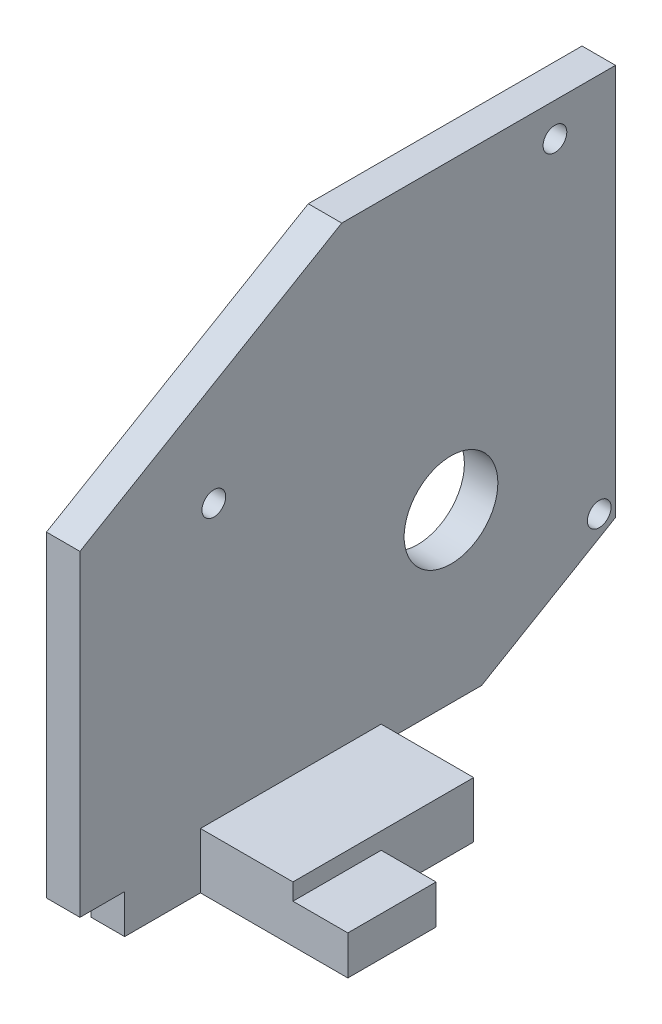
SolidWorks part; units mm, degrees
material "BRASS"
ref_plane "Front Plane" through (0, 0, 0) normal (0, 0, 1) x (1, 0, 0)
ref_plane "Top Plane" through (0, 0, 0) normal (0, 1, 0) x (1, 0, 0)
ref_plane "Right Plane" through (0, 0, 0) normal (1, 0, 0) x (0, 0, -1)
sketch "Sketch2" plane through (0, 0, 0) normal (1, 0, 0) x (0, 0, -1)
  line L6 (0, 0) -> (76.2, 0)
  line L7 (76.2, 0) -> (101.6111, 14.8934)
  line L10 (49.67, 89.2456) -> (0, 60.1339)
  line L12 (49.67, 89.2456) -> (101.6111, 89.1932)
  line L13 (101.6111, 89.1932) -> (101.6111, 14.8934)
  line L15 (0, 60.1339) -> (0, 0)
  line L16 (22.86, 0) -> (22.86, 3.175)
  line L17 (57.15, 0) -> (57.15, 3.175)
  line L18 (44.45, 0) -> (44.45, 3.175) construction
  line L19 (31.75, 0) -> (31.75, 3.175) construction
  line L20 (22.86, 3.175) -> (57.15, 3.175)
  line L21 (57.15, 0) -> (57.15, -7.4092)
  line L22 (57.15, -7.4092) -> (8.4806, -7.4092)
  line L23 (4.9187, -7.4092) -> (19.3272, -7.4092) construction
  line L24 (8.4806, -7.4092) -> (8.4806, 0)
  line L25 (22.86, 0) -> (22.86, -7.4092)
  line L26 (25.4, 55.3212) -> (70.4004, 31.75) construction
  line L27 (70.4004, 31.75) -> (98.5257, 17.018) construction
  circle A0 centre (25.4, 55.3212) radius 2.2479
  circle A1 centre (90.1192, 82.8548) radius 2.2479
  circle A3 centre (25.4, 55.3212) radius 50.8 construction
  circle A4 centre (70.4004, 31.75) radius 31.75 construction
  circle A5 centre (70.4004, 31.75) radius 8.89
  circle A6 centre (98.5257, 17.018) radius 2.2479
  point P22 (0, 0)
  point P23 (101.6111, 14.8934)
  point P30 (70.4004, 31.75)
  point P34 (0, 0)
  dimension "D3" = 4.4958
  dimension "D14" = 101.6
  dimension "D16" = 63.5
  dimension "D17" = 17.78
  dimension "D1" = 76.2
  dimension "D2" = 25.4
  dimension "D4" = 55.3212
  dimension "D5" = 82.8548
  dimension "D6" = 70.3326
  dimension "D7" = 40.4492
  dimension "D8" = 6.35
  dimension "D9" = 3.175
  dimension "D10" = 12.7
  dimension "D11" = 19.05
  dimension "D12" = 8.89
  dimension "D13" = 12.7
  dimension "D15" = 31.75
extrude "Boss-Extrude3" add sketch "Sketch2" against normal blind 6.35 contours L20 L16 L6 L17 | L16 L20 L17 L6 L7 L13 L12 L10 L15 A1 A0 | L6 L25 L22 L21 | L25 L6 L24 L22 region at (0, 43.299, -52.3587) region at (0, -3.7046, -15.6703) region at (0, 1.5875, -40.005) region at (0, -3.7046, -40.005)
extrude "Boss-Extrude4" add sketch "Sketch2<5>" along normal blind 17.5514 contours L20 L16 L6 L17 | L6 L25 L22 L21 region at (0, 1.5875, -40.005) region at (0, -3.7046, -40.005)
sketch "Sketch2<5>" plane through (0, 0, 0) normal (1, 0, 0) x (0, 0, -1) same geometry as "Sketch2"
sketch "Sketch3" plane through (17.5514, 0, 0) normal (1, 0, 0) x (0, 0, -1)
  line L0 (39.6, 0) -> (39.6, -7.4092)
  line L1 (57.15, -7.4092) -> (22.86, -7.4092) construction
  line L2 (39.6, 0) -> (39.6, -7.4092) construction
  line L3 (39.6, -7.4092) -> (22.86, -7.4092)
  line L4 (22.86, -7.4092) -> (22.86, 0)
  line L5 (22.86, -7.4092) -> (22.86, 3.175) construction
  line L6 (22.86, 0) -> (39.6, 0)
extrude "Boss-Extrude5" add sketch "Sketch3" along normal blind 10.414
